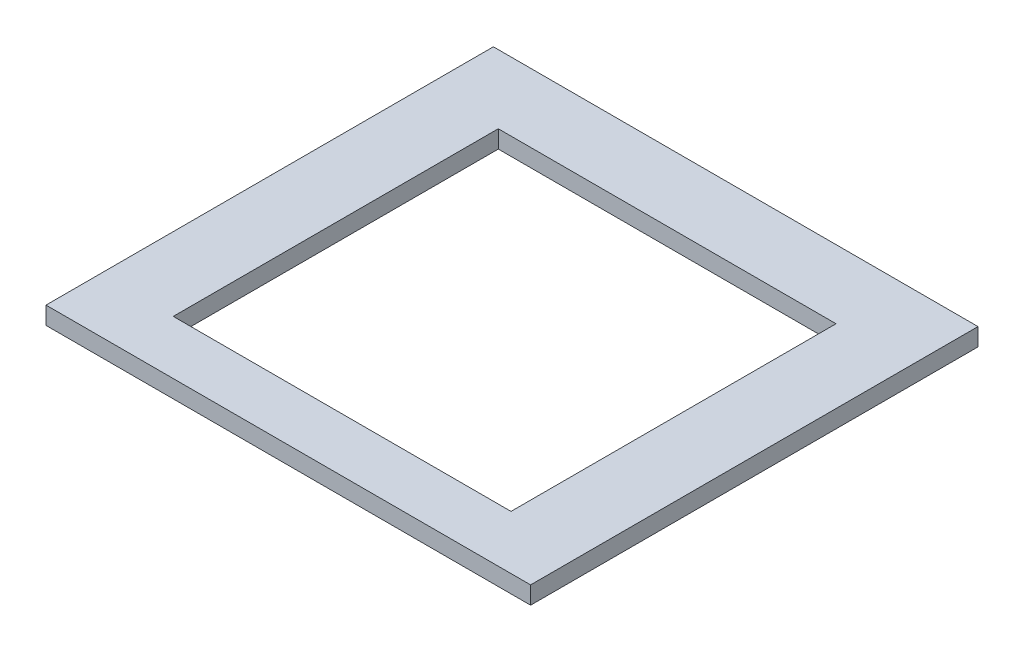
SolidWorks part; units mm, degrees
ref_plane "Front Plane" through (0, 0, 0) normal (0, 0, 1) x (1, 0, 0)
ref_plane "Top Plane" through (0, 0, 0) normal (0, 1, 0) x (1, 0, 0)
ref_plane "Right Plane" through (0, 0, 0) normal (1, 0, 0) x (0, 0, -1)
sketch "Sketch1" plane through (0, 0, 0) normal (0, 1, 0) x (1, 0, 0)
  line L1 (0, 0) -> (495, 0)
  line L2 (0, 0) -> (0, 457)
  line L3 (0, 457) -> (495, 457)
  line L4 (495, 0) -> (495, 457)
  line L5 (75, 387) -> (420, 387)
  line L6 (75, 387) -> (75, 55)
  line L7 (75, 55) -> (420, 55)
  line L8 (420, 387) -> (420, 55)
  dimension "D1" = 495
  dimension "D2" = 457
  dimension "D3" = 70
  dimension "D4" = 55
  dimension "D5" = 75
  dimension "D6" = 75
extrude "Boss-Extrude1" add sketch "Sketch1" along normal blind 18
